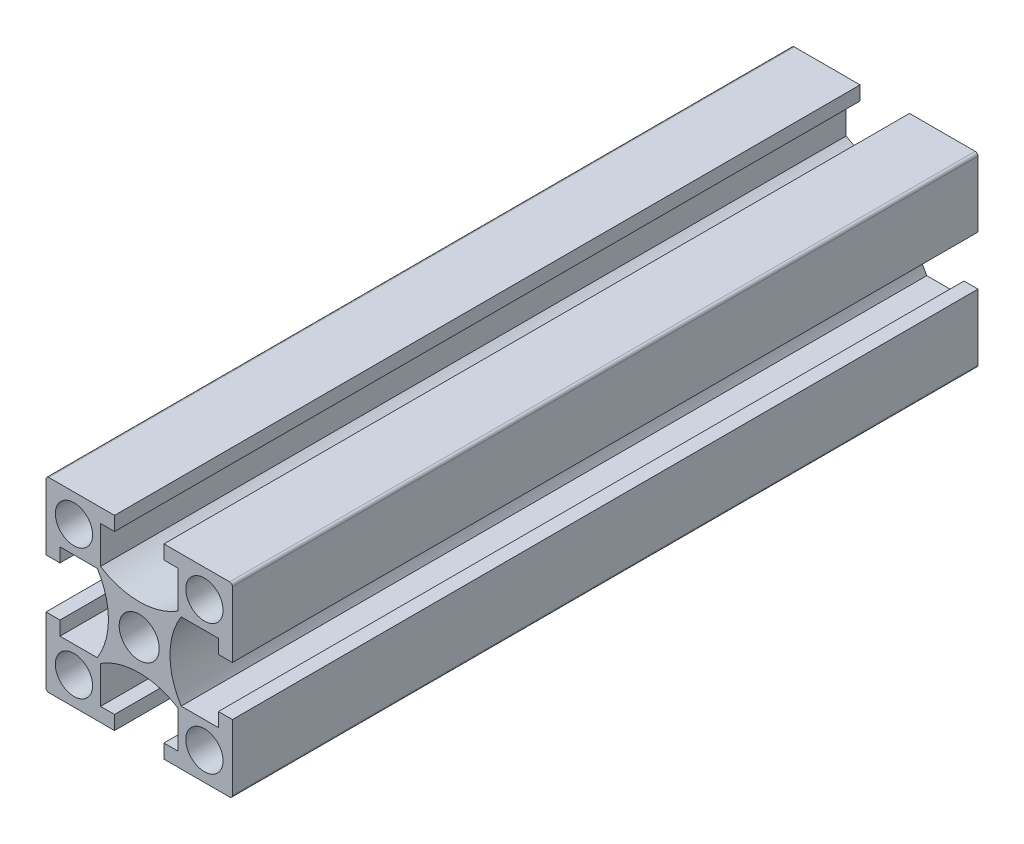
SolidWorks part; units mm, degrees
material "3.0255 (EN-AW 1350A)"
ref_plane "정면" through (0, 0, 0) normal (0, 0, 1) x (1, 0, 0)
ref_plane "윗면" through (0, 0, 0) normal (0, 1, 0) x (1, 0, 0)
ref_plane "우측면" through (0, 0, 0) normal (1, 0, 0) x (0, 0, -1)
sketch "스케치1" plane through (0, 0, 0) normal (0, 0, 1) x (1, 0, 0)
  line L0 (0, 32.0265) -> (0, -31.6588) construction
  line L1 (-10, 10) -> (-10, -10)
  line L2 (-10, 10) -> (10, 10)
  line L3 (-10, 2.65) -> (-8.5, 2.65)
  line L4 (13.6618, 0) -> (-11.6993, 0) construction
  line L5 (-8.5, 2.65) -> (-8.5, 4.15)
  line L6 (-8.5, 4.15) -> (-4.5032, 4.15)
  line L7 (-10, -2.65) -> (-8.5, -2.65)
  line L8 (-8.5, -2.65) -> (-8.5, -4.15)
  line L9 (-8.5, -4.15) -> (-4.5032, -4.15)
  line L10 (-10, -10) -> (10, -10)
  line L11 (10, 10) -> (10, -10)
  circle A0 centre (-7, 7) radius 2
  circle A1 centre (-7, -7) radius 2
  arc A2 (-4.5032, 4.15) -> (-4.5032, -4.15) centre (-11.0587, 0) cw
  circle A3 centre (0, 0) radius 2.15
  circle A4 centre (7, 7) radius 2
  circle A5 centre (7, -7) radius 2
  point P21 (-10, 0)
  point P23 (-3.3, 0)
  point P31 (0, -10)
  point P32 (0, 10)
  dimension "D3" = 4
  dimension "D9" = 6.7
  dimension "D10" = 4.3
  dimension "D11" = 7.7587
  dimension "D1" = 20
  dimension "D2" = 20
  dimension "D4" = 14
  dimension "D5" = 14
  dimension "D6" = 5.3
  dimension "D7" = 8.3
  dimension "D8" = 1.5
extrude "보스-돌출1" add sketch "스케치1" along normal blind 80 contours A0 | A4 | A3 | A5 | A1 | A2 L6 L5 L3 L1 L7 L8 L9 | L2 L11 L10 L1 region at (-6.6069, 0, 0) region at (-7, 7, 0) region at (-7, -7, 0) region at (0, 0, 0) region at (7, 7, 0) region at (7, -7, 0)
extrude "컷-돌출1" cut sketch "스케치1<3>" along normal up to next contours A2 L6 L5 L3 L1 L7 L8 L9 region at (-6.6069, 0, 0)
sketch "스케치1<3>" plane through (0, 0, 0) normal (0, 0, 1) x (1, 0, 0) same geometry as "스케치1"
pattern_circular "원형 패턴1" count 4 over 360 about axis through (0, 0, 80) along (0, 0, -1) of "컷-돌출1" reverse direction yes
fillet "필렛1" radius 0.3 4 edges at (10, -10, 40) (-10, -10, 40) (-10, 10, 40) (10, 10, 40)
sketch "스케치3" plane through (0, -10, 0) normal (0, -1, 0) x (1, 0, 0)
  line L0 (4.15, 80) -> (-4.15, 80) construction
  circle A0 centre (0, 70) radius 2.5
  circle A1 centre (0, 11) radius 2.5
  dimension "D1" = 10
  dimension "D2" = 11
extrude "컷-돌출2" cut sketch "스케치3" against normal through all
